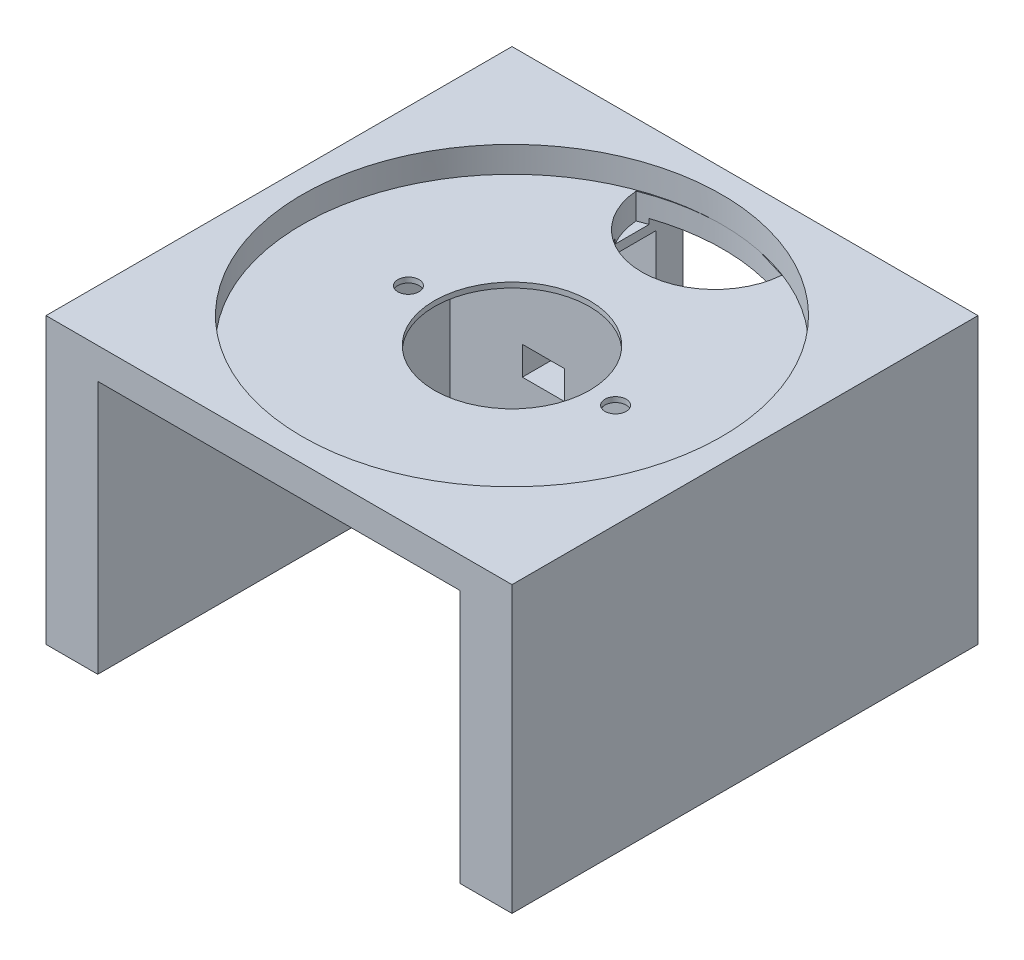
SolidWorks part; units mm, degrees
ref_plane "Front Plane" through (0, 0, 0) normal (0, 0, 1) x (1, 0, 0)
ref_plane "Top Plane" through (0, 0, 0) normal (0, 1, 0) x (1, 0, 0)
ref_plane "Right Plane" through (0, 0, 0) normal (1, 0, 0) x (0, 0, -1)
sketch "Sketch1" plane through (0, 0, 0) normal (0, 1, 0) x (1, 0, 0)
  line L2 (0, -45) -> (-45, -45)
  line L3 (-45, -45) -> (-45, 45)
  line L4 (-45, 45) -> (0, 45)
  line L5 (0, 45) -> (45, 45)
  line L6 (45, 45) -> (45, -45)
  line L7 (45, -45) -> (0, -45)
extrude "Boss-Extrude1" add sketch "Sketch1" along normal blind 10
sketch "Sketch2" plane through (0, 10, 0) normal (0, 1, 0) x (1, 0, 0)
  circle A0 centre (0, 0) radius 40.5
extrude "Cut-Extrude1" cut sketch "Sketch2" against normal blind 5 contours A0
sketch "Sketch4" plane through (0, 5, 0) normal (0, 1, 0) x (1, 0, 0)
  circle A2 centre (-20, 0) radius 2.05
  circle A3 centre (20, 0) radius 2.05
extrude "Cut-Extrude2" cut sketch "Sketch4" against normal blind 2
sketch "Sketch5" plane through (0, 5, 0) normal (0, 1, 0) x (1, 0, 0)
  circle A0 centre (0, 0) radius 15
extrude "Cut-Extrude3" cut sketch "Sketch5" against normal through all
sketch "Sketch7" plane through (0, 5, 0) normal (0, 1, 0) x (1, 0, 0)
  arc A0 (-13.8415, 37.8005) -> (14.3106, 37.8005) centre (0.2345, 38.9392) ccw
  arc A1 (-13.8415, 37.8005) -> (14.3106, 37.8005) centre (0.2345, 2.5037) cw
extrude "Cut-Extrude4" cut sketch "Sketch7" against normal blind 66 contours A0 A1
sketch "Sketch8" plane through (0, 0, 0) normal (0, -1, 0) x (1, 0, 0)
  line L0 (-45, 45) -> (45, 45)
  line L1 (45, 45) -> (45, -45)
  line L2 (45, -45) -> (-45, -45)
  line L3 (-45, -45) -> (-45, 45)
extrude "Boss-Extrude2" add sketch "Sketch8" along normal blind 45
sketch "Sketch9" plane through (0, 0, 45) normal (0, 0, 1) x (1, 0, 0)
  line L0 (-45, -45) -> (-35, -45)
  line L1 (45, -45) -> (-45, -45) construction
  line L2 (-35, -45) -> (-35, 4)
  line L3 (-35, 4) -> (35, 4)
  line L4 (35, 4) -> (35, -45)
  line L5 (35, -45) -> (-35, -45)
extrude "Cut-Extrude5" cut sketch "Sketch9" against normal blind 68 contours L2 L3 L4 L5
sketch "Sketch10" plane through (0, 0, -45) normal (0, 0, -1) x (-1, 0, 0)
  line L8 (0, 10) -> (0, -45) construction
  line L9 (-45, 10) -> (45, 10) construction
  line L13 (45, -45) -> (-45, -45) construction
  line L14 (-45, -17.5) -> (45, -17.5) construction
  line L15 (-45, 10) -> (-45, -45) construction
  line L16 (45, 10) -> (45, -45) construction
  line L29 (-12, -21) -> (-12, -25)
  line L36 (-12, -25) -> (-18, -25)
  line L37 (-12, -21) -> (-12, -2)
  line L39 (-12, -2) -> (-12, 1)
  line L40 (-12, 1) -> (12, 1)
  line L41 (12, -25) -> (12, 1)
  line L42 (12, -25) -> (18.3379, -25)
  line L43 (-18, -25) -> (-18, -37)
  line L44 (18.3379, -25) -> (18.3379, -37)
  line L45 (18.3379, -37) -> (-18, -37)
extrude "Cut-Extrude7" cut sketch "Sketch10" against normal blind 21
sketch "Sketch12" plane through (0, 0, -45) normal (0, 0, -1) x (-1, 0, 0)
  text T0 "ProtoPill\r\nDispenser\r\nTester"
extrude "Cut-Extrude9" cut sketch "Sketch12" against normal blind 4
sketch "Sketch17" plane through (0, -37, 0) normal (0, 1, 0) x (1, 0, 0)
  line L0 (-0.1689, 24) -> (-0.1689, 45) construction
  line L1 (18, 24) -> (-18.3379, 24) construction
  line L2 (18, 45) -> (-18.3379, 45) construction
  line L3 (18, 34.5) -> (-18.3379, 34.5) construction
  line L4 (18, 24) -> (18, 45) construction
  line L5 (-18.3379, 24) -> (-18.3379, 45) construction
  line L6 (11.8311, 34.5) -> (11.8311, 26.5)
  line L7 (-12.1689, 34.5) -> (-12.1689, 42.5)
  line L8 (-12.1689, 34.5) -> (-12.1689, 26.5)
  line L9 (11.8311, 34.5) -> (11.8311, 42.5)
  line L10 (11.8311, 26.5) -> (-12.1689, 26.5)
  line L11 (-12.1689, 42.5) -> (11.8311, 42.5)
extrude "Cut-Extrude12" cut sketch "Sketch17" against normal blind 3
sketch "Sketch18" plane through (0, -40, 0) normal (0, 1, 0) x (1, 0, 0)
  circle A0 centre (-0.1689, 32.5) radius 11.15
  dimension "D1" = 22.3
extrude "Cut-Extrude13" cut sketch "Sketch18" against normal blind 4.66
sketch "Sketch20" plane through (-12, 0, 0) normal (1, 0, 0) x (0, 0, -1)
  line L0 (34.5, -25) -> (34.5, 0) construction
  line L1 (24, -25) -> (45, -25) construction
  line L2 (38.4803, 0) -> (31.8859, 0) construction
  line L3 (24, -12) -> (45, -12) construction
  line L4 (24, -25) -> (24, 1) construction
  line L5 (45, -25) -> (45, 1) construction
  line L6 (29.17, -12) -> (29.17, -1.7)
  line L7 (39.83, -12) -> (39.83, -1.7)
  line L8 (39.83, -12) -> (39.83, -22.3)
  line L9 (29.17, -12) -> (29.17, -22.3)
  line L10 (29.17, -1.7) -> (39.83, -1.7)
  line L11 (39.83, -22.3) -> (29.17, -22.3)
extrude "Cut-Extrude14" cut sketch "Sketch20" against normal blind 9
sketch "Sketch21" plane through (0, 0, -29.17) normal (0, 0, -1) x (-1, 0, 0)
  line L1 (21, -1.7) -> (21, -22.3) construction
  line L2 (21, -22.3) -> (12, -22.3) construction
  line L3 (21, -22.3) -> (21, -16.8)
  line L7 (12.8896, -16.8) -> (12.8896, -22.3)
  line L8 (12.8896, -22.3) -> (21, -22.3)
  line L9 (12.8896, -16.8) -> (21, -16.8)
  dimension "D1" = 8.1104
  dimension "D2" = 5.5
extrude "Cut-Extrude15" cut sketch "Sketch21" against normal blind 9
sketch "Sketch22" plane through (-21, 0, 0) normal (1, 0, 0) x (0, 0, -1)
  line L0 (34.5, -1.7) -> (34.5, -22.3) construction
  line L1 (39.83, -1.7) -> (29.17, -1.7) construction
  line L2 (23, -22.3) -> (39.83, -22.3) construction
  line L3 (39.83, -12) -> (29.17, -12) construction
  line L4 (39.83, -22.3) -> (39.83, -1.7) construction
  line L5 (29.17, -1.7) -> (29.17, -16.8) construction
  circle A0 centre (34.5, -17.05) radius 1.14
  dimension "D1" = 2.28
extrude "Boss-Extrude3" add sketch "Sketch22" along normal blind 9
sketch "Sketch24" plane through (12, 0, 0) normal (-1, 0, 0) x (0, 0, 1)
  line L0 (-39.83, -1.7) -> (-29.17, -1.7) construction
  line L1 (-29.17, -22.3) -> (-39.83, -22.3) construction
  line L2 (-39.83, -22.3) -> (-39.83, -1.7) construction
  line L3 (-29.17, -1.7) -> (-29.17, -22.3) construction
  line L4 (-39.83, -1.7) -> (-29.17, -1.7)
  line L5 (-29.17, -22.3) -> (-39.83, -22.3)
  line L6 (-39.83, -22.3) -> (-39.83, -1.7)
  line L7 (-29.17, -1.7) -> (-29.17, -22.3)
  circle A0 centre (-34.5, -17.05) radius 1.14 construction
  circle A1 centre (-34.5, -17.05) radius 1.14
extrude "Cut-Extrude16" cut sketch "Sketch24" against normal blind 9
sketch "Sketch25" plane through (0, 0, -29.17) normal (0, 0, -1) x (-1, 0, 0)
  line L0 (-21, -22.3) -> (-21, -16.8)
  line L1 (-21, -22.3) -> (-21, -1.7) construction
  line L2 (-21, -16.8) -> (-12.89, -16.8)
  line L3 (-12.89, -16.8) -> (-12.89, -22.3)
  line L4 (-21, -22.3) -> (-12, -22.3) construction
  line L5 (-12.89, -22.3) -> (-21, -22.3)
extrude "Cut-Extrude17" cut sketch "Sketch25" against normal blind 9
sketch "Sketch32" plane through (0, 0, -23) normal (0, 0, 1) x (1, 0, 0)
  line L0 (-6.0061, -40) -> (-6.0061, -44.66)
  line L9 (-0.1689, -40) -> (-0.1689, -44.66) construction
  line L10 (-5.1007, -40) -> (4.7628, -40) construction
  line L11 (10.9811, -44.66) -> (-11.3189, -44.66) construction
  line L25 (10.9711, -40) -> (5.6682, -40)
  line L26 (-11.3089, -40) -> (-11.3089, -44.66)
  line L27 (-11.3089, -44.66) -> (-6.0061, -44.66)
  line L28 (-11.3089, -40) -> (-6.0061, -40)
  line L29 (10.9711, -44.66) -> (5.6682, -44.66)
  line L30 (10.9711, -40) -> (10.9711, -44.66)
  line L31 (5.6682, -40) -> (5.6682, -44.66)
extrude "Cut-Extrude21" cut sketch "Sketch32" against normal blind 10
